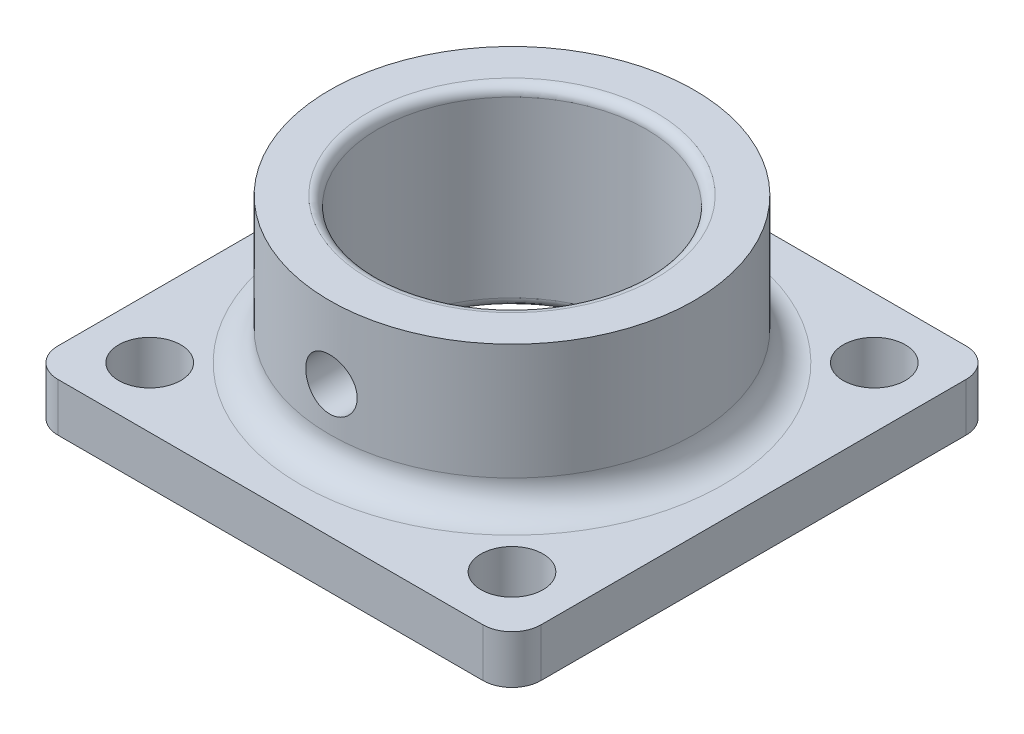
SolidWorks part; units mm, degrees
ref_plane "Front Plane" through (0, 0, 0) normal (0, 0, 1) x (1, 0, 0)
ref_plane "Top Plane" through (0, 0, 0) normal (0, 1, 0) x (1, 0, 0)
ref_plane "Right Plane" through (0, 0, 0) normal (1, 0, 0) x (0, 0, -1)
sketch "Sketch1" plane through (0, 0, 0) normal (0, 1, 0) x (1, 0, 0)
  line L1 (-12.7, 12.7) -> (12.7, 12.7)
  line L2 (-12.7, 12.7) -> (-12.7, -12.7)
  line L3 (-12.7, -12.7) -> (12.7, -12.7)
  line L4 (12.7, 12.7) -> (12.7, -12.7)
  dimension "D1" = 12.7
  dimension "D2" = 25.4
  dimension "D3" = 12.7
  dimension "D4" = 25.4
extrude "Boss-Extrude1" add sketch "Sketch1" along normal blind 2.54
ref_plane "Plane1" through (0, 2.54, 0) normal (0, 1, 0) x (1, 0, 0)
sketch "Sketch2" plane through (0, 2.54, 0) normal (0, 1, 0) x (1, 0, 0)
  circle A0 centre (0, 0) radius 7.0485
  dimension "D1" = 14.097
extrude "Extrude-Thin1" add sketch "Sketch2" along normal blind 7.62 thin thin type one direction wall 2.54
sketch "Sketch3" plane through (0, 2.54, 0) normal (0, 1, 0) x (1, 0, 0)
  line L0 (0, 5.1443) -> (0, -4.0492)
  point P0 (-9.525, 9.525)
  point P1 (9.525, -9.525)
  point P5 (-9.525, -9.525)
  point P6 (9.525, 9.525)
  dimension "D1" = 9.525
  dimension "D2" = 9.525
  dimension "D3" = 9.525
  dimension "D4" = 9.525
ref_plane "Plane2" through (0, 0, 12.7) normal (0, 0, 1) x (1, 0, 0)
sketch "Sketch11" plane through (0, 0, 12.7) normal (0, 0, 1) x (1, 0, 0)
  line L0 (-12.7, 2.54) -> (-12.7, 0) construction
  point P0 (0, 6.35)
  point P1 (-12.7, 1.27)
  dimension "D1" = 6.35
  dimension "D2" = 12.7
hole_wizard "Tap Drill for #6-32 Tap1" positions "Sketch13" profile "Sketch12" hole size "#6-32" standard "ANSI Inch"
sketch "Sketch13" plane through (0, 0, 12.7) normal (0, 0, 1) x (1, 0, 0)
  point P0 (0, 6.35)
sketch "Sketch12" plane through (0, 6.35, 12.7) normal (1, 0, 0) x (0, -1, 0)
  line L0 (0, 0) -> (0, 13.5127)
  line L1 (0, 13.5127) -> (1.3525, 12.7)
  line L2 (1.3525, 12.7) -> (1.3525, 0)
  line L5 (1.3525, 0) -> (0, 0)
  line L10 (0, 13.5127) -> (-1.3526, 12.7) construction
  line L11 (0, -6.35) -> (0, 107.95) construction
  dimension "Hole Dia." = 2.7051
  dimension "Hole Depth" = 12.7
  dimension "Drill Angle" = 118
fillet "Fillet1" radius 1.524 1 edges at (9.5885, 2.54, 0)
fillet "Fillet2" radius 1.524 4 edges at (-12.7, 1.27, -12.7) (12.7, 1.27, -12.7) (-12.7, 1.27, 12.7) (12.7, 1.27, 12.7)
sketch "Sketch14" plane through (0, 2.54, 0) normal (0, 1, 0) x (1, 0, 0)
extrude "Cut-Extrude1" cut sketch "Sketch2<2>" against normal blind 7.62
sketch "Sketch2<2>" plane through (0, 2.54, 0) normal (0, 1, 0) x (1, 0, 0) same geometry as "Sketch2"
fillet "Fillet3" radius 0.508 2 edges at (0, 0, 7.0485) (0, 10.16, 7.0485)
hole_wizard "#4 Clearance Hole4" positions "Sketch18" profile "Sketch19" hole size "#4" standard "ANSI Inch"
sketch "Sketch18" plane through (0, 2.54, 0) normal (0, 1, 0) x (1, 0, 0)
  point P0 (9.525, 9.525)
  point P3 (9.525, -9.525)
  point P6 (-9.525, -9.525)
  point P9 (-9.525, 9.525)
sketch "Sketch19" plane through (9.525, 2.54, -9.525) normal (1, 0, 0) x (0, 0, 1)
  line L0 (0, 0) -> (0, 3.5206)
  line L1 (0, 3.5206) -> (1.6319, 2.54)
  line L2 (1.6319, 2.54) -> (1.6319, 0)
  line L5 (1.6319, 0) -> (0, 0)
  line L10 (0, 3.5206) -> (-1.632, 2.54) construction
  line L11 (0, -6.35) -> (0, 107.95) construction
  dimension "Hole Dia." = 3.2639
  dimension "Hole Depth" = 2.54
  dimension "Drill Angle" = 118
